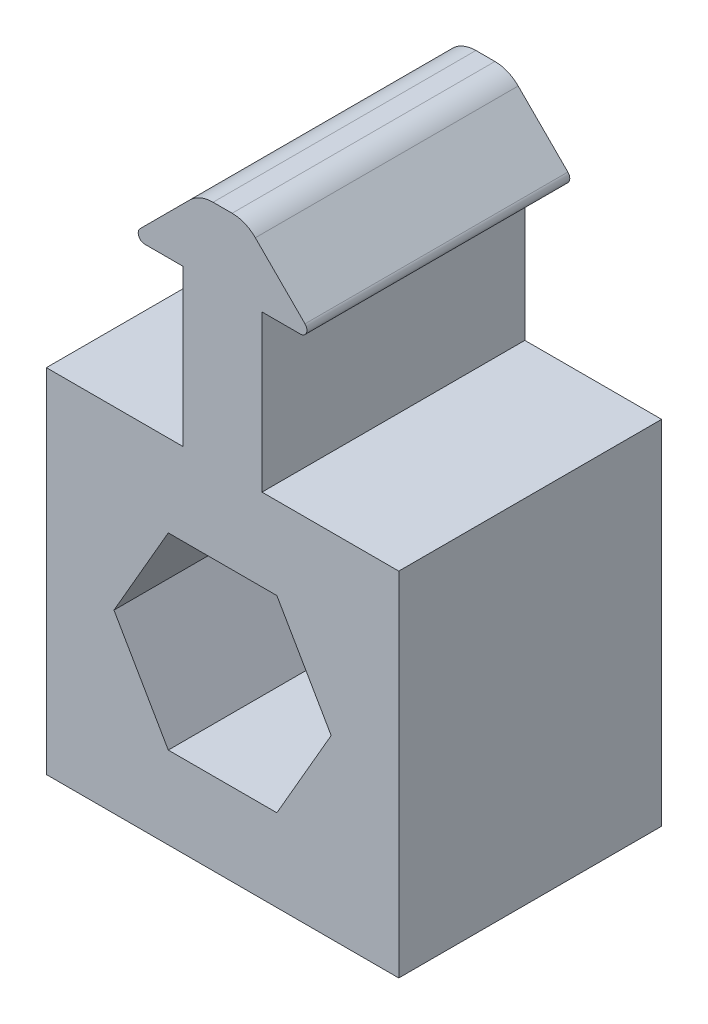
SolidWorks part; units mm, degrees
ref_plane "Front Plane" through (0, 0, 0) normal (0, 0, 1) x (1, 0, 0)
ref_plane "Top Plane" through (0, 0, 0) normal (0, 1, 0) x (1, 0, 0)
ref_plane "Right Plane" through (0, 0, 0) normal (1, 0, 0) x (0, 0, -1)
sketch "Sketch1" plane through (0, 0, 0) normal (0, 0, 1) x (1, 0, 0)
  line L0 (-13.6207, 13.6208) -> (-13.6207, -13.6207)
  line L1 (-4.1978, 7.2708) -> (-8.3955, 0)
  line L2 (-8.3955, 0) -> (-4.1978, -7.2707)
  line L3 (-4.1978, -7.2707) -> (4.1978, -7.2707)
  line L4 (4.1978, -7.2707) -> (8.3955, 0)
  line L5 (8.3955, 0) -> (4.1978, 7.2708)
  line L6 (4.1978, 7.2708) -> (-4.1978, 7.2708)
  line L7 (-13.6207, -13.6207) -> (13.6208, -13.6207)
  line L8 (13.6208, -13.6207) -> (13.6208, 13.6208)
  line L9 (-13.6207, 13.6208) -> (-3.048, 13.6208)
  line L10 (-3.048, 13.6208) -> (-3.048, 25.6857)
  line L11 (-3.048, 25.6857) -> (-6.0126, 25.6857)
  line L12 (-6.3718, 26.553) -> (-2.5321, 30.3926)
  line L13 (-0.7361, 31.1366) -> (0.7361, 31.1366)
  line L14 (0, 41.8096) -> (0, -25.778) construction
  line L15 (13.6208, 13.6208) -> (3.048, 13.6207)
  line L16 (3.048, 13.6207) -> (3.048, 25.6857)
  line L17 (6.3718, 26.553) -> (2.5321, 30.3926)
  line L18 (3.048, 25.6857) -> (6.0126, 25.6857)
  circle A0 centre (0, 0) radius 7.2707 construction
  arc A1 (-6.0126, 25.6857) -> (-6.3718, 26.553) centre (-6.0126, 26.1938) cw
  arc A2 (-2.5321, 30.3926) -> (-0.7361, 31.1366) centre (-0.7361, 28.5966) cw
  arc A3 (2.5321, 30.3926) -> (0.7361, 31.1366) centre (0.7361, 28.5966) ccw
  arc A4 (6.0126, 25.6857) -> (6.3718, 26.553) centre (6.0126, 26.1938) ccw
  point P18 (7.239, 25.6857)
  point P21 (-4.5303, 25.6857)
  point P25 (-7.239, 25.6857)
  point P29 (0, -13.6208)
  point P35 (0, 31.1366)
  dimension "D7" = 0.508
  dimension "D8" = 2.54
  dimension "D1" = 14.5415
  dimension "D2" = 18.415
  dimension "D3" = 6.096
  dimension "D4" = 5.4508
  dimension "D5" = 135
  dimension "D6" = 14.478
  dimension "D9" = 6.35
  dimension "D10" = 6.35
extrude "Boss-Extrude1" add sketch "Sketch1" along normal mid plane 20.32
sketch "Sketch8" plane through (13.6208, 0, 0) normal (1, 0, 0) x (0, 0, -1)
  line L0 (-10.16, 13.6207) -> (10.16, 13.6207) construction
  line L1 (-7.024, 13.6207) -> (-5.5, 13.6207)
  line L2 (-7.024, 13.6207) -> (-7.024, 1.4456)
  line L3 (-7.024, 1.4456) -> (-5.5, 1.4456)
  line L4 (-5.5, 13.6207) -> (-5.5, 1.4456)
  line L10 (0, 20.1653) -> (0, -17.7306) construction
  dimension "D1" = 11
  dimension "D2" = 1.524
